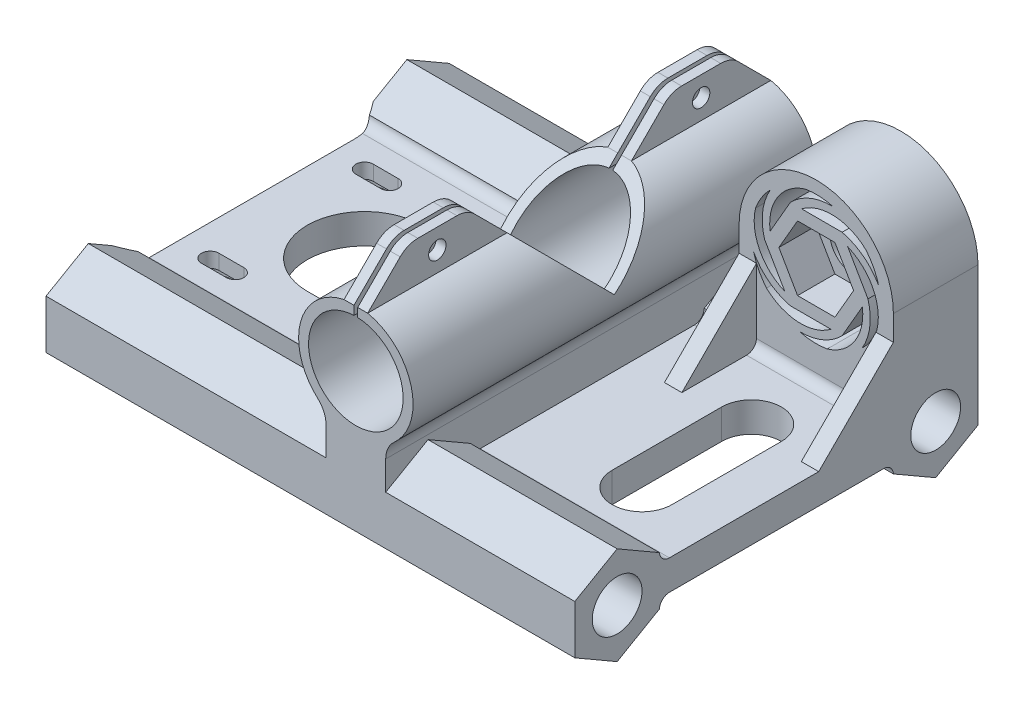
SolidWorks part; units mm, degrees
ref_plane "Front Plane" through (0, 0, 0) normal (0, 0, 1) x (1, 0, 0)
ref_plane "Top Plane" through (0, 0, 0) normal (0, 1, 0) x (1, 0, 0)
ref_plane "Right Plane" through (0, 0, 0) normal (1, 0, 0) x (0, 0, -1)
sketch "Sketch2" plane through (0, 0, 0) normal (1, 0, 0) x (0, 0, -1)
  line L0 (-5.6113, 0) -> (58.3887, 0) construction
  line L1 (2.8887, 3) -> (49.8887, 3)
  line L2 (66.8887, 4.9075) -> (58.3887, 9.815)
  line L3 (58.3887, 9.815) -> (49.8887, 4.9075)
  line L4 (49.8887, 4.9075) -> (49.8887, 3)
  line L5 (49.8887, -4.9075) -> (58.3887, -9.815)
  line L6 (58.3887, -9.815) -> (66.8887, -4.9075)
  line L7 (66.8887, -4.9075) -> (66.8887, 4.9075)
  line L8 (2.8887, 4.9075) -> (-5.6113, 9.815)
  line L9 (-5.6113, 9.815) -> (-14.1113, 4.9075)
  line L10 (-14.1113, 4.9075) -> (-14.1113, -4.9075)
  line L11 (-14.1113, -4.9075) -> (-5.6113, -9.815)
  line L12 (-5.6113, -9.815) -> (2.8887, -4.9075)
  line L13 (2.8887, -4.9075) -> (2.8887, -3)
  line L14 (2.8887, -3) -> (49.8887, -3)
  line L15 (49.8887, -3) -> (49.8887, -4.9075)
  line L16 (2.8887, 3) -> (2.8887, 4.9075)
  circle A2 centre (58.3887, 0) radius 8.5 construction
  circle A3 centre (-5.6113, 0) radius 8.5 construction
  dimension "D2" = 17
  dimension "D3" = 47
  dimension "D4" = 6
  dimension "D5" = 3
extrude "Boss-Extrude1" add sketch "Sketch2" along normal blind 106.25
sketch "Sketch3" plane through (0, 3, 0) normal (0, 1, 0) x (1, 0, 0)
  line L0 (0, 49.8887) -> (47, 2.8887) construction
  line L1 (106.25, 2.8887) -> (0, 2.8887) construction
  line L2 (0, 2.8887) -> (47, 49.8887) construction
  line L3 (106.25, 49.8887) -> (0, 49.8887) construction
  line L4 (106.25, 2.8887) -> (0, 2.8887) construction
  line L5 (1.75, 48.1387) -> (1.75, 2.8887)
  line L6 (39, 41.8887) -> (8, 41.8887) construction
  line L7 (39, 41.8887) -> (39, 10.8887) construction
  line L8 (39, 10.8887) -> (8, 10.8887) construction
  line L9 (8, 41.8887) -> (8, 10.8887) construction
  line L10 (1.75, 48.1387) -> (45.25, 48.1387) construction
  line L11 (45.25, 48.1387) -> (45.25, 4.6387) construction
  line L12 (45.25, 4.6387) -> (1.75, 4.6387) construction
  line L13 (1.75, 2.8887) -> (0, -0.8613)
  line L14 (0, 2.8887) -> (0, -5.6113) construction
  line L15 (8, 41.8887) -> (13, 41.8887) construction
  line L16 (1.75, 48.1387) -> (1.75, 49.8887)
  line L17 (8, 43.6387) -> (13, 43.6387)
  line L18 (1.75, 49.8887) -> (0, 51.6387)
  line L19 (8, 40.1387) -> (13, 40.1387)
  line L20 (0, 58.3887) -> (0, 49.8887) construction
  line L21 (0, 51.6387) -> (0, -0.8613)
  line L22 (39, 41.8887) -> (44, 41.8887) construction
  line L23 (39, 43.6387) -> (44, 43.6387)
  line L24 (39, 40.1387) -> (44, 40.1387)
  line L25 (39, 10.8887) -> (44, 10.8887) construction
  line L26 (39, 12.6387) -> (44, 12.6387)
  line L27 (39, 9.1387) -> (44, 9.1387)
  line L28 (8, 10.8887) -> (13, 10.8887) construction
  line L29 (8, 12.6387) -> (13, 12.6387)
  line L30 (8, 9.1387) -> (13, 9.1387)
  line L31 (23.5, 26.3887) -> (28.5, 26.3887) construction
  line L32 (23.5, 37.8887) -> (28.5, 37.8887)
  line L33 (23.5, 14.8887) -> (28.5, 14.8887)
  circle A0 centre (23.5, 26.3887) radius 11.5 construction
  circle A1 centre (39, 41.8887) radius 1.75 construction
  circle A2 centre (39, 10.8887) radius 1.75 construction
  circle A3 centre (8, 10.8887) radius 1.75 construction
  circle A4 centre (8, 41.8887) radius 1.75 construction
  arc A5 (8, 43.6387) -> (8, 40.1387) centre (8, 41.8887) ccw
  arc A6 (13, 40.1387) -> (13, 43.6387) centre (13, 41.8887) ccw
  arc A7 (39, 43.6387) -> (39, 40.1387) centre (39, 41.8887) ccw
  arc A8 (44, 40.1387) -> (44, 43.6387) centre (44, 41.8887) ccw
  arc A9 (39, 12.6387) -> (39, 9.1387) centre (39, 10.8887) ccw
  arc A10 (44, 9.1387) -> (44, 12.6387) centre (44, 10.8887) ccw
  arc A11 (8, 12.6387) -> (8, 9.1387) centre (8, 10.8887) ccw
  arc A12 (13, 9.1387) -> (13, 12.6387) centre (13, 10.8887) ccw
  arc A13 (23.5, 37.8887) -> (23.5, 14.8887) centre (23.5, 26.3887) ccw
  arc A14 (28.5, 14.8887) -> (28.5, 37.8887) centre (28.5, 26.3887) ccw
  point P24 (10.5, 41.8887)
  point P40 (41.5, 41.8887)
  point P46 (41.5, 10.8887)
  point P52 (10.5, 10.8887)
  point P58 (26, 26.3887)
  dimension "D4" = 3.5
  dimension "D5" = 23
  dimension "D12" = 1.75
  dimension "D13" = 11.5
  dimension "D1" = 45
  dimension "D2" = 45
  dimension "D3" = 31
  dimension "D6" = 43.5
  dimension "D7" = 5
  dimension "D8" = 5
  dimension "D9" = 5
  dimension "D10" = 5
  dimension "D11" = 5
extrude "Cut-Extrude1" cut sketch "Sketch3" against normal blind 28 and the other way blind 30
fillet "Fillet3" radius 2 4 edges at (54, -3, -2.8887) (54, -3, -49.8887) (54, 3, -49.8887) (54, 3, -2.8887)
sketch "Sketch4" plane through (0, 0, -66.8887) normal (0, 0, -1) x (-1, 0, 0)
  line L0 (-62.25, 3) -> (-62.25, 23) construction
  line L1 (-106.25, 3) -> (-1.75, 3) construction
  line L3 (-68.25, 3) -> (-68.25, 13.1893)
  line L4 (-56.25, 3) -> (-56.25, 13.1893)
  line L5 (-56.25, 3) -> (-68.25, 3)
  line L6 (-59.875, 34.2521) -> (-59.875, 42.2521)
  line L7 (-59.875, 42.2521) -> (-61.875, 42.2521)
  line L8 (-61.875, 42.2521) -> (-61.875, 32.4926)
  line L9 (-64.625, 34.2521) -> (-64.625, 42.2521)
  line L10 (-64.625, 42.2521) -> (-62.625, 42.2521)
  line L11 (-62.625, 42.2521) -> (-62.625, 32.4926)
  line L12 (-1.75, 4.9075) -> (-1.75, -4.9075) construction
  arc A0 (-62.625, 32.4926) -> (-61.875, 32.4926) centre (-62.25, 23) ccw
  arc A1 (-56.25, 13.1893) -> (-59.875, 34.2521) centre (-62.25, 23) ccw
  arc A3 (-64.625, 34.2521) -> (-68.25, 13.1893) centre (-62.25, 23) ccw
  dimension "D1" = 2
  dimension "D2" = 2
  dimension "D3" = 0.75
  dimension "D10" = 8
  dimension "D6" = 19
  dimension "D7" = 23
  dimension "D4" = 12
  dimension "D5" = 6
  dimension "D8" = 20
  dimension "D9" = 0.375
  dimension "D11" = 60.5
extrude "Boss-Extrude2" add sketch "Sketch4" against normal up to surface (81 mm away) up to face at (53.125, 0, 14.1113)
fillet "Fillet4" radius 5 2 edges at (56.25, 13.1893, -26.3887) (68.25, 13.1893, -26.3887)
sketch "Sketch5" plane through (0, 0, -66.8887) normal (0, 0, -1) x (-1, 0, 0)
  line L0 (-62.25, 23) -> (-110, 23) construction
  line L1 (-106.25, 23) -> (-106.25, 4.9075)
  line L2 (-106.25, 4.9075) -> (-68.25, 4.9075) construction
  line L3 (-106.25, 4.9075) -> (-75.25, 4.9075)
  line L4 (-75.25, 4.9075) -> (-75.25, 23)
  circle A0 centre (-90.75, 23) radius 4.75
  arc A1 (-75.25, 23) -> (-106.25, 23) centre (-90.75, 23) ccw
  arc A2 (-62.625, 32.4926) -> (-61.875, 32.4926) centre (-62.25, 23) ccw construction
  dimension "D1" = 9.5
  dimension "D3" = 31
  dimension "D4" = 0
  dimension "D5" = 28.5
  dimension "D2" = 28.5
extrude "Boss-Extrude7" add sketch "Sketch5" against normal up to vertex (17 mm away) up to point (68.25, 4.9075, -49.8887)
sketch "Sketch6" plane through (0, 0, -49.8887) normal (0, 0, 1) x (1, 0, 0)
  line L0 (106.25, 9.815) -> (68.25, 9.815) construction
  line L1 (83.2444, 23) -> (86.9972, 16.5)
  line L2 (86.9972, 16.5) -> (94.5028, 16.5)
  line L3 (94.5028, 16.5) -> (98.2556, 23)
  line L4 (98.2556, 23) -> (94.5028, 29.5)
  line L5 (94.5028, 29.5) -> (86.9972, 29.5)
  line L6 (86.9972, 29.5) -> (83.2444, 23)
  circle A0 centre (90.75, 23) radius 6.5 construction
  dimension "D1" = 13
extrude "Cut-Extrude2" cut sketch "Sketch6" against normal blind 7.5
sketch "Sketch7" plane through (0, 0, 0) normal (-1, 0, 0) x (0, 0, 1)
  line L0 (14.1113, 42.2521) -> (-66.8887, 42.2521) construction
  line L1 (-66.8887, 34.2521) -> (-38.8887, 34.2521) construction
  line L2 (-66.8887, 34.2521) -> (-66.8887, 14.4284) construction
  line L3 (-66.8887, 14.4284) -> (-38.8887, 14.4284) construction
  line L4 (-38.8887, 34.2521) -> (-38.8887, 14.4284) construction
  line L6 (14.1113, 14.4284) -> (-13.8887, 14.4284) construction
  line L7 (14.1113, 14.4284) -> (14.1113, 34.2521) construction
  line L8 (14.1113, 34.2521) -> (-13.8887, 34.2521) construction
  line L9 (-13.8887, 14.4284) -> (-13.8887, 34.2521) construction
  line L10 (14.1113, 38.2521) -> (-67.3887, 38.2521) construction
  line L11 (14.1113, 14.4284) -> (14.1113, 34.2521) construction
  line L12 (-38.8887, 42.2521) -> (-66.8887, 42.2521) construction
  line L13 (-52.8887, 34.2521) -> (-52.8887, 42.2521) construction
  line L15 (0.1113, 34.2521) -> (0.1113, 42.2521) construction
  line L16 (-38.8887, 34.2521) -> (-26.3887, 21.7521)
  line L17 (-13.8887, 34.2521) -> (-26.3887, 21.7521)
  line L18 (-13.8887, 34.2521) -> (-13.8887, 42.2521)
  line L19 (-38.8887, 34.2521) -> (-38.8887, 42.2521)
  line L20 (-38.8887, 42.2521) -> (-13.8887, 42.2521)
  line L21 (-66.8887, 14.4284) -> (14.1113, 14.4284) construction
  line L22 (-13.8887, 42.2521) -> (14.1113, 42.2521) construction
  line L25 (14.1113, 42.2521) -> (14.1113, 34.2521) construction
  line L26 (14.1113, 34.2521) -> (-66.8887, 34.2521) construction
  circle A0 centre (0.1113, 38.2521) radius 1.75
  circle A1 centre (-52.8887, 38.2521) radius 1.75
  dimension "D3" = 3.5
  dimension "D1" = 28
  dimension "D2" = 28
  dimension "D4" = 45
  dimension "D5" = 45
extrude "Cut-Extrude3" cut sketch "Sketch7" against normal up to surface (75.25 mm away) up to face at (75.25, 13.126, -58.3887)
chamfer "Chamfer1" distance 8 angle 45 8 edges at (60.875, 42.2521, -66.8887) (63.625, 42.2521, -66.8887) (63.625, 42.2521, -38.8887) (60.875, 42.2521, -38.8887) (63.625, 42.2521, 14.1113) (60.875, 42.2521, 14.1113) (60.875, 42.2521, -13.8887) (63.625, 42.2521, -13.8887)
fillet "Fillet5" radius 5 8 edges at (60.875, 42.2521, 6.1113) (63.625, 42.2521, 6.1113) (63.625, 42.2521, -5.8887) (60.875, 42.2521, -5.8887) (60.875, 42.2521, -46.8887) (63.625, 42.2521, -46.8887) (63.625, 42.2521, -58.8887) (60.875, 42.2521, -58.8887)
sketch "Sketch9" plane through (106.25, 0, 0) normal (1, 0, 0) x (0, 0, -1)
  line L0 (-9.8613, 7.3612) -> (-1.3613, -7.3612) construction
  line L1 (-5.6113, 9.815) -> (-14.1113, 4.9075) construction
  line L2 (-5.6113, -9.815) -> (2.8887, -4.9075) construction
  line L3 (54.1387, -7.3612) -> (62.6387, 7.3612) construction
  line L4 (49.8887, -4.9075) -> (58.3887, -9.815) construction
  circle A0 centre (58.3887, 0) radius 5
  circle A1 centre (-5.6113, 0) radius 5
  dimension "D1" = 10
extrude "Cut-Extrude5" cut sketch "Sketch9" against normal up to surface (50 mm away) up to face at (56.25, 6.5862, -26.3887)
sketch "Sketch14" plane through (0, 3, 0) normal (0, 1, 0) x (1, 0, 0)
  line L0 (91.25, 64.8887) -> (91.25, -14.1113) construction
  line L3 (106.25, 47.8909) -> (106.25, 4.8866) construction
  line L4 (91.25, 36.3887) -> (91.25, 14.3887) construction
  line L5 (97.25, 36.3887) -> (97.25, 14.3887)
  line L6 (85.25, 36.3887) -> (85.25, 14.3887)
  line L8 (106.25, -14.1113) -> (68.25, -14.1113) construction
  arc A0 (97.25, 36.3887) -> (85.25, 36.3887) centre (91.25, 36.3887) ccw
  arc A1 (85.25, 14.3887) -> (97.25, 14.3887) centre (91.25, 14.3887) ccw
  point P10 (91.25, 25.3887)
  dimension "D2" = 6
  dimension "D1" = 15
  dimension "D3" = 22
extrude "Cut-Extrude8" cut sketch "Sketch14" against normal blind 10
fillet "Fillet7" radius 10 2 edges at (1.75, 0, -2.8887) (1.75, 0, -49.8887)
sketch "Sketch16" plane through (106.25, 0, 0) normal (1, 0, 0) x (0, 0, -1)
  line L0 (49.8887, 18) -> (49.8887, 3)
  line L1 (49.8887, 23) -> (49.8887, 4.9075) construction
  line L3 (49.8887, 3) -> (34.8887, 3)
  line L4 (47.8909, 3) -> (4.8866, 3) construction
  line L5 (34.8887, 3) -> (49.8887, 18)
  dimension "D1" = 15
extrude "Boss-Extrude8" add sketch "Sketch16" against normal blind 3.5
sketch "Sketch17" plane through (75.25, 0, 0) normal (-1, 0, 0) x (0, 0, 1)
  line L0 (-49.8887, 18) -> (-34.8887, 3)
  line L1 (-34.8887, 3) -> (-49.8887, 3)
  line L2 (-49.8887, 3) -> (-49.8887, 18)
extrude "Boss-Extrude9" add sketch "Sketch17" against normal blind 3.5
sketch "Sketch18" plane through (0, 0, -49.8887) normal (0, 0, 1) x (1, 0, 0)
  line L2 (95.9462, 32) -> (85.5538, 32) construction
  line L3 (85.5538, 32) -> (80.3577, 23) construction
  line L4 (80.3577, 23) -> (85.5538, 14) construction
  line L5 (85.5538, 14) -> (95.9462, 14) construction
  line L6 (95.9462, 14) -> (101.1423, 23) construction
  line L7 (101.1423, 23) -> (95.9462, 32) construction
  line L8 (94.5028, 29.5) -> (86.9972, 29.5) construction
  line L9 (98.2556, 23) -> (94.5028, 29.5) construction
  line L10 (95.9462, 32) -> (87.7959, 32)
  line L11 (101.1423, 23) -> (97.0672, 30.0583)
  line L12 (95.9462, 14) -> (100.0213, 21.0583)
  line L13 (85.5538, 14) -> (93.7041, 14)
  line L14 (80.3577, 23) -> (84.4328, 15.9417)
  line L15 (85.5538, 32) -> (81.4787, 24.9417)
  circle A0 centre (90.75, 23) radius 9 construction
  arc A1 (103.3135, 26.3402) -> (100.7453, 31.3123) centre (90.75, 23) ccw construction
  arc A3 (106.25, 23) -> (75.25, 23) centre (90.75, 23) ccw construction
  arc A4 (95.9462, 32) -> (103.3135, 26.3402) centre (93.221, 20.8276) cw
  arc A5 (97.0672, 30.0583) -> (102.9463, 18.5) centre (93.221, 20.8276) cw
  arc A6 (95.5907, 30.5427) -> (101.9971, 25.6212) centre (93.221, 20.8276) cw construction
  arc A7 (101.1423, 23) -> (99.9245, 13.7898) centre (90.1041, 19.7739) cw
  arc A8 (100.0213, 21.0583) -> (92.951, 10.1877) centre (90.1041, 19.7739) cw
  arc A9 (95.9462, 14) -> (87.361, 10.4495) centre (87.6331, 21.9463) cw
  arc A10 (93.7041, 14) -> (80.7547, 14.6877) centre (87.6331, 21.9463) cw
  arc A11 (85.5538, 14) -> (78.1865, 19.6598) centre (88.279, 25.1724) cw
  arc A12 (84.4328, 15.9417) -> (78.5537, 27.5) centre (88.279, 25.1724) cw
  arc A13 (80.3577, 23) -> (81.5755, 32.2102) centre (91.3959, 26.2261) cw
  arc A14 (81.4787, 24.9417) -> (88.549, 35.8123) centre (91.3959, 26.2261) cw
  arc A15 (85.5538, 32) -> (94.139, 35.5505) centre (93.8669, 24.0537) cw
  arc A16 (87.7959, 32) -> (100.7453, 31.3123) centre (93.8669, 24.0537) cw
  arc A17 (103.3135, 26.3402) -> (100.7453, 31.3123) centre (90.75, 23) ccw
  arc A18 (94.139, 35.5505) -> (88.549, 35.8123) centre (90.75, 23) ccw construction
  arc A19 (94.139, 35.5505) -> (88.549, 35.8123) centre (90.75, 23) ccw
  arc A20 (81.5755, 32.2102) -> (78.5537, 27.5) centre (90.75, 23) ccw construction
  arc A21 (81.5755, 32.2102) -> (78.5537, 27.5) centre (90.75, 23) ccw
  arc A22 (78.1865, 19.6598) -> (80.7547, 14.6877) centre (90.75, 23) ccw construction
  arc A23 (78.1865, 19.6598) -> (80.7547, 14.6877) centre (90.75, 23) ccw
  arc A24 (87.361, 10.4495) -> (92.951, 10.1877) centre (90.75, 23) ccw construction
  arc A25 (87.361, 10.4495) -> (92.951, 10.1877) centre (90.75, 23) ccw
  arc A26 (99.9245, 13.7898) -> (102.9463, 18.5) centre (90.75, 23) ccw construction
  arc A27 (99.9245, 13.7898) -> (102.9463, 18.5) centre (90.75, 23) ccw
  point P56 (90.75, 23)
  dimension "D1" = 2.5
  dimension "D3" = 1.5
  dimension "D5" = 11.5
  dimension "D2" = 2.5
  dimension "D4" = 4.5
  dimension "D6" = 6
extrude "Cut-Extrude9" cut sketch "Sketch18" against normal up to surface (17 mm away) up to face at (61.6667, 17.1213, -66.8887)
sketch "Sketch20" plane through (0, -3, 0) normal (0, -1, 0) x (1, 0, 0)
  line L0 (8, -10.8887) -> (13, -10.8887) construction
  line L1 (8, -6.3887) -> (13, -6.3887)
  line L2 (8, -15.3887) -> (13, -15.3887)
  line L3 (39, -10.8887) -> (44, -10.8887) construction
  line L4 (39, -6.3887) -> (44, -6.3887)
  line L5 (39, -15.3887) -> (44, -15.3887)
  line L6 (39, -41.8887) -> (44, -41.8887) construction
  line L7 (39, -37.3887) -> (44, -37.3887)
  line L8 (39, -46.3887) -> (44, -46.3887)
  line L9 (13, -41.8887) -> (8, -41.8887) construction
  line L10 (13, -46.3887) -> (8, -46.3887)
  line L11 (13, -37.3887) -> (8, -37.3887)
  arc A0 (8, -6.3887) -> (8, -15.3887) centre (8, -10.8887) ccw
  arc A1 (13, -15.3887) -> (13, -6.3887) centre (13, -10.8887) ccw
  arc A2 (39, -6.3887) -> (39, -15.3887) centre (39, -10.8887) ccw
  arc A3 (44, -15.3887) -> (44, -6.3887) centre (44, -10.8887) ccw
  arc A4 (39, -37.3887) -> (39, -46.3887) centre (39, -41.8887) ccw
  arc A5 (44, -46.3887) -> (44, -37.3887) centre (44, -41.8887) ccw
  arc A6 (13, -46.3887) -> (13, -37.3887) centre (13, -41.8887) ccw
  arc A7 (8, -37.3887) -> (8, -46.3887) centre (8, -41.8887) ccw
  point P4 (10.5, -10.8887)
  point P9 (41.5, -10.8887)
  point P18 (41.5, -41.8887)
  point P27 (10.5, -41.8887)
  dimension "D1" = 4.5
extrude "Cut-Extrude10" cut sketch "Sketch20" against normal blind 3
